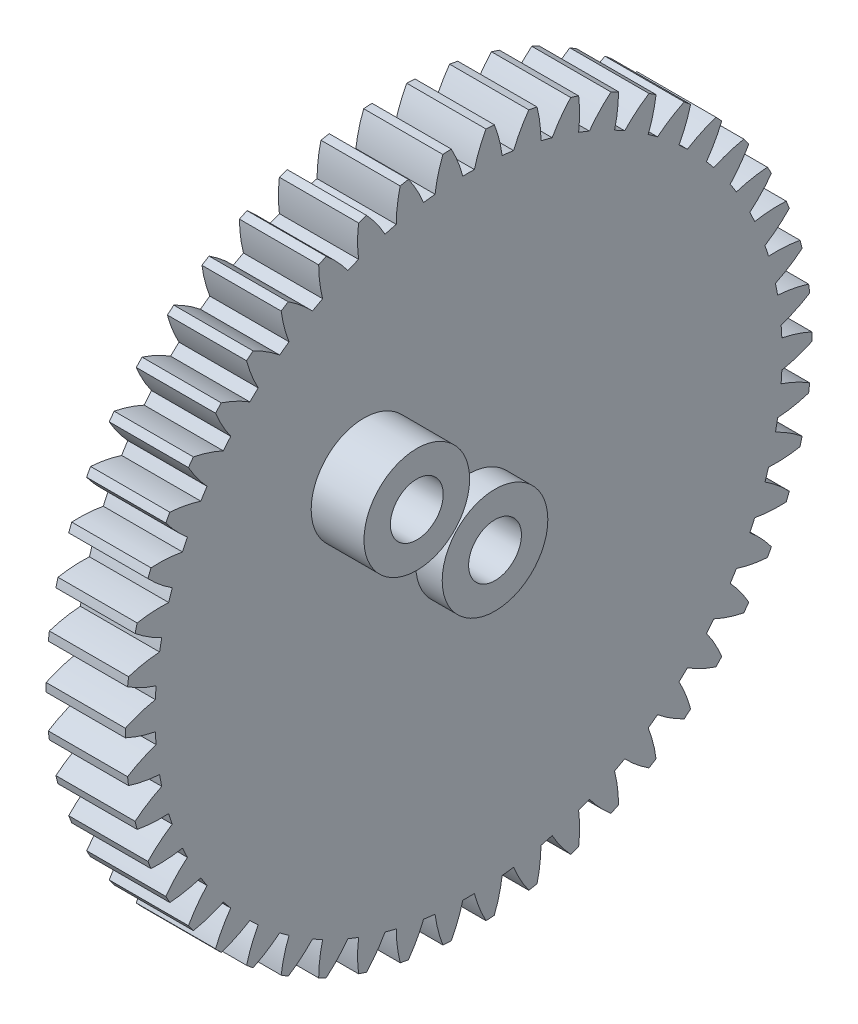
SolidWorks part; units mm, degrees
ref_plane "Plane1" through (0, 0, 0) normal (0, 0, 1) x (1, 0, 0)
ref_plane "Plane2" through (0, 0, 0) normal (0, 1, 0) x (1, 0, 0)
ref_plane "Plane3" through (0, 0, 0) normal (1, 0, 0) x (0, 0, -1)
other "Configuration Table"
sketch "HoldingSke" plane through (0, 0, 0) normal (0, 1, 0) x (1, 0, 0)
  line L0 (0, 0) -> (1.2856, -1.5321)
  line L1 (-15, 0) -> (100, 0) construction
  line L2 (0, 0) -> (-2.1039, 2.3779)
  line L3 (0, 0) -> (-11.863, 4.5341)
  line L4 (0, 0) -> (5.5511, 6.6156)
  line L5 (0, 0) -> (-46.8476, -17.4728)
  line L6 (0, 0) -> (-2.4869, -1.6779)
  line L7 (-2.1039, 2.3779) -> (8.6586, 51.2059)
  line L8 (-76.2, 54.61) -> (-75.9, 54.61)
  line L9 (-71.009, 38.7566) -> (-53.1078, 45.2721)
  line L10 (-76.2, 71.12) -> (104.1128, 71.12)
  line L11 (0, 0) -> (-3, 0)
  line L12 (-76.2, 101.6) -> (-76.181, 101.6)
  line L13 (24.9733, 27.94) -> (52.9518, 28.4284)
  line L14 (24.9733, 27.94) -> (24.9743, 27.94)
  line L15 (24.9733, 27.94) -> (100.4006, 29.5858)
  line L16 (-63.627, -0.5) -> (-12.827, -0.5)
  circle A0 centre (0, 0) radius 1
  circle A1 centre (0, 0) radius 11.874
  circle A2 centre (0, 0) radius 37.5
  circle A3 centre (0, 0) radius 1
  dimension "Num_teeth" = 50
  dimension "Pitch_radius" = 180.3128
  dimension "Width" = 3
  dimension "Thickness" = 3
sketch "BasProSke" plane through (0, 0, 0) normal (0, 1, 0) x (1, 0, 0)
  line L0 (-10, 0) -> (60, 0) construction
  line L1 (0, 0) -> (0, 13)
  line L2 (0, 0) -> (3, 0)
  line L3 (3, 0) -> (3, 13)
  line L4 (3, 13) -> (0, 13)
  dimension "Thickness" = 3
  dimension "Diameter" = 26
revolve "Base-Revolve" add sketch "BasProSke" angle 360 about L0
sketch "TooCutSke" plane through (0, 0, 0) normal (1, 0, 0) x (0, 0, -1)
  line L1 (0, 0) -> (0, 107) construction
  line L2 (0, 0) -> (-0.4259, 12.4927) construction
  line L3 (0, 0) -> (-1.5691, 24.9404) construction
  line L4 (-0.4259, 12.4927) -> (-0.7846, 12.4702) construction
  arc A0 (0.2187, 11.872) -> (-0.2187, 11.872) centre (0, 0) ccw
  arc A1 (0.6715, 13.0081) -> (-0.6715, 13.0081) centre (0, 0) ccw
  circle A2 centre (0, 0) radius 12.5 construction
  circle A3 centre (0, 0) radius 11.7462 construction
  arc A4 (-0.2187, 11.872) -> (-0.6715, 13.0081) centre (-5.0549, 10.6028) ccw
  arc A5 (0.6715, 13.0081) -> (0.2187, 11.872) centre (5.0549, 10.6028) ccw
extrude "ToothCut" cut sketch "TooCutSke" along normal through all
fillet "Breaks" [suppressed] radius 0.01 tangent propagation no
fillet "RootFillets" [suppressed] radius 0.126
pattern_circular "TeethCuts" count 50 every 7.2 about axis through (-10, 0, 0) along (1, 0, 0) of "ToothCut", "RootFillets", "Breaks"
sketch "HubNeaOneSke" plane through (0, 0, 0) normal (-1, 0, 0) x (0, 0, 1)
  circle A0 centre (0, 0) radius 11.874
  dimension "Diameter" = 23.748
extrude "HubNearOne" [suppressed] add sketch "HubNeaOneSke" along normal blind 47.0001
sketch "HubNeaBotSke" plane through (0, 0, 0) normal (-1, 0, 0) x (0, 0, 1)
  circle A0 centre (0, 0) radius 11.874
  dimension "Diameter" = 23.748
extrude "HubNearBoth" [suppressed] add sketch "HubNeaBotSke" along normal blind 23.5
ref_plane "FarPln" through (3, 0, 0) normal (1, 0, 0) x (0, 0, -1)
sketch "HubFarSke" plane through (3, 0, 0) normal (1, 0, 0) x (0, 0, -1)
  circle A0 centre (0, 0) radius 11.874
  dimension "Diameter" = 23.748
extrude "HubFar" [suppressed] add sketch "HubFarSke" along normal blind 23.5
sketch "BorSke" plane through (0, 0, 0) normal (1, 0, 0) x (0, 0, -1)
  circle A0 centre (0, 0) radius 1
  dimension "Diameter" = 2
extrude "Bore" cut sketch "BorSke" along normal mid plane 100.0001
sketch "KeySke" plane through (0, 0, 0) normal (1, 0, 0) x (0, 0, -1)
  line L0 (-0.4, 0) -> (-0.4, 1.3)
  line L1 (-0.4, 1.3) -> (0.4, 1.3)
  line L2 (0.4, 1.3) -> (0.4, 0)
  line L3 (0, 0) -> (0, 34) construction
  line L4 (-0.4, 0) -> (0.4, 0)
  dimension "Width" = 0.8
extrude "Keyway" [suppressed] cut sketch "KeySke" along normal mid plane 100.0001
pattern_circular "Keyway2" [suppressed] count 2 every 90 about axis through (-10, 0, 0) along (1, 0, 0)
sketch "草图1" plane through (3, 0, 0) normal (1, 0, 0) x (0, 0, -1)
  circle A0 centre (-3.9622, 3.8146) radius 1
  circle A1 centre (0, 0) radius 1 construction
  dimension "D1" = 5.5
extrude "切除-拉伸1" cut sketch "草图1" against normal through all
sketch "草图2" plane through (0, 0, 0) normal (-1, 0, 0) x (0, 0, 1)
  circle A0 centre (0, 0) radius 4
  circle A1 centre (0, 0) radius 1
extrude "凸台-拉伸1" add sketch "草图2" along normal blind 1.5
fillet "圆角1" radius 1.5 1 edges at (-1.5, 0, 4)
sketch "草图3" plane through (3, 0, 0) normal (1, 0, 0) x (0, 0, -1)
  circle A0 centre (-3.9622, 3.8146) radius 2
  circle A1 centre (-3.9622, 3.8146) radius 1
extrude "凸台-拉伸2" add sketch "草图3" along normal blind 2
sketch "草图5" plane through (3, 0, 0) normal (1, 0, 0) x (0, 0, -1)
  circle A0 centre (0, 0) radius 2
  circle A3 centre (0, 0) radius 1
extrude "凸台-拉伸3" add sketch "草图5" along normal blind 1
equation "' \"Module@HoldingSke\" = 6.35"
equation "' \"Num_teeth@HoldingSke\" = 12"
equation "' \"Ap@HoldingSke\" =  20"
equation "' \"Ap@HoldingSke\" = 20"
equation "' \"Width@HoldingSke\" = 0.5 * 25.4"
equation "' \"Hub_dia@HoldingSke\"= 1 * 25.4"
equation "' \"Hub_dia@HoldingSke\" = 1 * 25.4"
equation "' \"Overall_len@HoldingSke\" = 1.0 * 25.4"
equation "' \"Bore@HoldingSke\" = 0.75 * 25.4"
equation "' \"T_dim@HoldingSke\" = 0.1 * 25.4"
equation "' \"Width@KeySke\" = 0.25 * 25.4"
equation "' \"Show_teeth@HoldingSke\" = 13"
equation "' \"Backlash@HoldingSke\" = 0.009 * 25.4"
equation "' \"Addendum_fac@HoldingSke\" = 1.0"
equation "' \"Dedendum_fac@HoldingSke\" = 1.25"
equation "' \"Dedendum_add@HoldingSke\" = 0.00005 * 25.4"
equation "' \"Clearance_fac@HoldingSke\" = 0.25"
equation "\"Pitch@HoldingSke\" = 1 / \"Module@HoldingSke\""
equation "\"Overcut_dia@TooCutSke\" = (\"Num_teeth@HoldingSke\" + 2 * \"Addendum_fac@HoldingSke\") / \"Pitch@HoldingSke\" + 0.002 * 25.4"
equation "\"Pitch_dia@TooCutSke\" = \"Num_teeth@HoldingSke\" / \"Pitch@HoldingSke\""
equation "\"Base_dia@TooCutSke\" = \"Num_teeth@HoldingSke\" / \"Pitch@HoldingSke\" * cos((\"Ap@HoldingSke\"  * 3.14159265 / 180))"
equation "\"Root_dia@TooCutSke\" = (\"Num_teeth@HoldingSke\" + 2) / \"Pitch@HoldingSke\" - 2 * (\"Addendum_fac@HoldingSke\" + \"Dedendum_fac@HoldingSke\") / \"Pitch@HoldingSke\" - \"Dedendum_add@HoldingSke\" * 2"
equation "\"Half_ang@TooCutSke\" = 180 / \"Num_teeth@HoldingSke\""
equation "\"Half_CT@TooCutSke\" = \"Num_teeth@HoldingSke\" / \"Pitch@HoldingSke\" * sin((3.14159265 / 2 / \"Num_teeth@HoldingSke\")) / 2 - 7 * \"Backlash@HoldingSke\" / 4"
equation "\"Flank_rad@TooCutSke\" = \"Num_teeth@HoldingSke\" / \"Pitch@HoldingSke\" / 5"
equation "\"Radius@RootFillets\" = \"Clearance_fac@HoldingSke\" / \"Pitch@HoldingSke\" + \"Dedendum_add@HoldingSke\""
equation "\"Break_rad@Breaks\" = 0.02 / \"Pitch@HoldingSke\""
equation "\"Thickness@HoldingSke\" = \"Width@HoldingSke\""
equation "\"OAL@HoldingSke\" = \"Thickness@HoldingSke\""
equation "\"MHD@HoldingSke\" = (\"Num_teeth@HoldingSke\" + 2) / \"Pitch@HoldingSke\" - 2 * (\"Addendum_fac@HoldingSke\" + \"Dedendum_fac@HoldingSke\")  / \"Pitch@HoldingSke\" - \"Dedendum_add@HoldingSke\" * 2"
equation "\"MBD@HoldingSke\" = (\"Num_teeth@HoldingSke\" + 2) / \"Pitch@HoldingSke\" - 2 * (\"Addendum_fac@HoldingSke\" + \"Dedendum_fac@HoldingSke\")  / \"Pitch@HoldingSke\" - \"Dedendum_add@HoldingSke\" * 2 - 0.002 * 25.4"
equation "\"MHD@HoldingSke\" = ((sgn( \"MHD@HoldingSke\" - \"Hub_dia@HoldingSke\" )-1)*( \"MHD@HoldingSke\" - \"Hub_dia@HoldingSke\" ))/-2+ \"Hub_dia@HoldingSke\""
equation "\"MBD@HoldingSke\" = ((sgn( \"MBD@HoldingSke\" - \"Bore@HoldingSke\" )-1)*( \"MBD@HoldingSke\" - \"Bore@HoldingSke\" ))/-2+ \"Bore@HoldingSke\""
equation "\"OAL@HoldingSke\" = ((sgn( \"OAL@HoldingSke\" - \"Overall_len@HoldingSke\" )+1)*( \"OAL@HoldingSke\" - \"Overall_len@HoldingSke\" ))/2 + \"Overall_len@HoldingSke\" + 0.000002 * 25.4"
equation "\"Num_teeth@TeethCuts\" = int( \"Show_teeth@HoldingSke\" ) + 1"
equation "\"Num_teeth@TeethCuts\" = ((sgn( \"Num_teeth@TeethCuts\" - \"Num_teeth@HoldingSke\" )-1)*( \"Num_teeth@TeethCuts\" - \"Num_teeth@HoldingSke\" ))/-2+ \"Num_teeth@HoldingSke\""
equation "\"Num_teeth@TeethCuts\" = ((sgn( \"Num_teeth@TeethCuts\" - 2.0)+1)*( \"Num_teeth@TeethCuts\" - 2.0))/2 +2.0"
equation "\"Angle@TeethCuts\" = 360.0 / \"Num_teeth@HoldingSke\""
equation "\"Diameter@BasProSke\" = (\"Num_teeth@HoldingSke\" + 2 * \"Addendum_fac@HoldingSke\") / \"Pitch@HoldingSke\""
equation "\"Thickness@BasProSke\"  = \"Thickness@HoldingSke\""
equation "' \"Fillet_rad@BasProSke\" =  \"Thickness@HoldingSke\" * 0.05"
equation "' \"Fillet_rad@BasProSke\" = \"Thickness@HoldingSke\" * 0.05"
equation "\"MHD@HoldingSke\" = ((sgn( \"MHD@HoldingSke\" - \"Root_dia@TooCutSke\" )-1)*( \"MHD@HoldingSke\" - \"Root_dia@TooCutSke\" ))/-2+ \"Root_dia@TooCutSke\""
equation "\"Diameter@HubNeaOneSke\" = \"MHD@HoldingSke\""
equation "\"Length@HubNearOne\" = \"OAL@HoldingSke\" - \"Thickness@BasProSke\""
equation "\"Diameter@HubNeaBotSke\" = \"MHD@HoldingSke\""
equation "\"Length@HubNearBoth\" = ( \"OAL@HoldingSke\" - \"Thickness@BasProSke\" ) / 2.0"
equation "\"Thickness@FarPln\" = \"Thickness@BasProSke\""
equation "\"Diameter@HubFarSke\" = \"MHD@HoldingSke\""
equation "\"Length@HubFar\" = ( \"OAL@HoldingSke\" - \"Thickness@BasProSke\" ) / 2.0"
equation "\"Diameter@BorSke\" = \"MBD@HoldingSke\""
equation "\"D1@Bore\" = \"OAL@HoldingSke\" * 2.0"
equation "\"D1@Keyway\" = \"OAL@HoldingSke\" * 2.0"
equation "\"Offset@KeySke\" = \"T_dim@HoldingSke\" + \"MBD@HoldingSke\" / 2.0"
